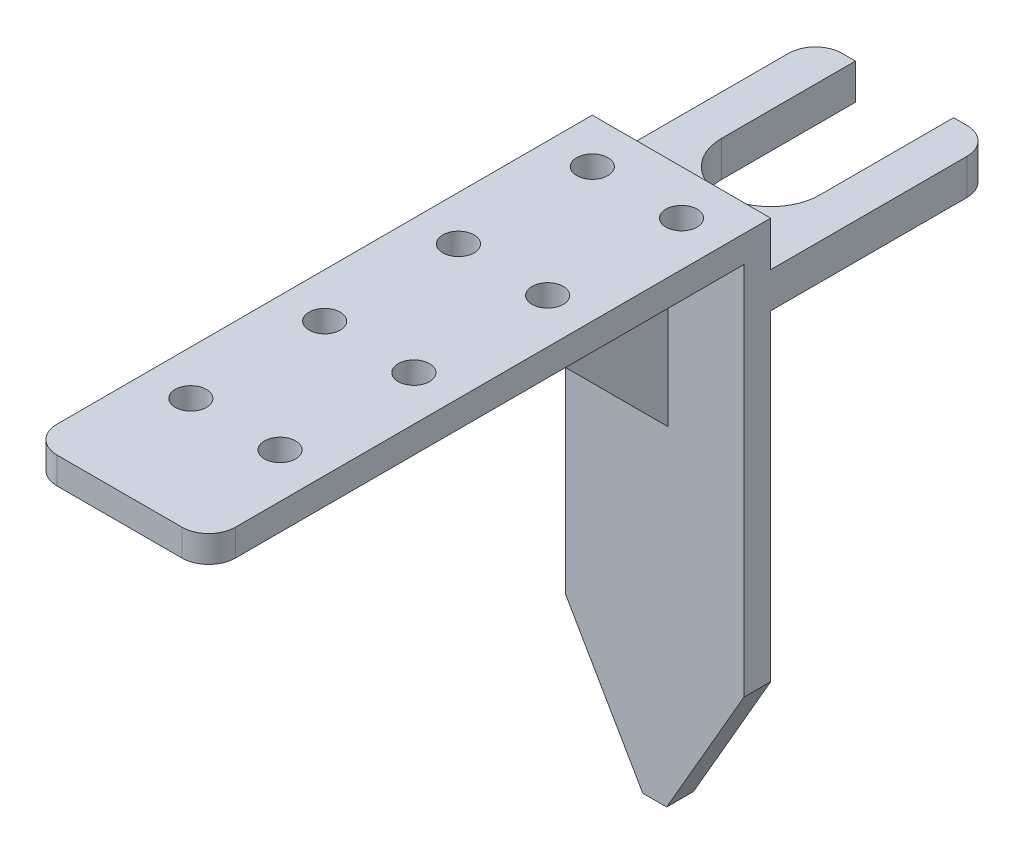
SolidWorks part; units mm, degrees
ref_plane "Front Plane" through (0, 0, 0) normal (0, 0, 1) x (1, 0, 0)
ref_plane "Top Plane" through (0, 0, 0) normal (0, 1, 0) x (1, 0, 0)
ref_plane "Right Plane" through (0, 0, 0) normal (1, 0, 0) x (0, 0, -1)
sketch "Sketch1" plane through (0, 0, 0) normal (0, 0, 1) x (1, 0, 0)
  line L1 (-10, 30) -> (10, 30)
  line L2 (-10, 30) -> (-10, -30)
  line L3 (-10, -30) -> (10, -30)
  line L4 (10, 30) -> (10, -30)
  line L5 (-10, 30) -> (10, -30) construction
  line L6 (-10, -30) -> (10, 30) construction
  point P0 (0, 0)
  dimension "D1" = 20
  dimension "D2" = 60
extrude "Boss-Extrude1" add sketch "Sketch1" along normal blind 3
sketch "Sketch2" plane through (0, 0, 3) normal (0, 0, 1) x (1, 0, 0)
  line L0 (10, -30) -> (10, 30) construction
  line L1 (-10, 30) -> (10, 30)
  line L2 (-10, 30) -> (-10, 27)
  line L3 (-10, 27) -> (10, 27)
  line L4 (10, 30) -> (10, 27)
  dimension "D1" = 3
extrude "Boss-Extrude2" add sketch "Sketch2" along normal blind 60
sketch "Sketch3" plane through (0, 27, 0) normal (0, -1, 0) x (1, 0, 0)
  line L0 (-10, 3) -> (10, 3) construction
  line L1 (-1.5, 3) -> (1.5, 3)
  line L2 (-1.5, 3) -> (-1.5, 18)
  line L3 (-1.5, 18) -> (1.5, 18)
  line L4 (1.5, 3) -> (1.5, 18)
  line L5 (0, 3) -> (0, 0) construction
  dimension "D1" = 3
  dimension "D2" = 15
extrude "Boss-Extrude3" add sketch "Sketch3" along normal blind 20
chamfer "Chamfer1" distance 15 angle 45 1 edges at (0, 7, 18)
sketch "Sketch4" plane through (0, 27, 0) normal (0, -1, 0) x (1, 0, 0)
  line L0 (-5, 5) -> (5, 5) construction
  line L1 (0, 5) -> (0, 0) construction
  circle A0 centre (-5, 5) radius 1.75
  circle A1 centre (5, 5) radius 1.75
  dimension "D1" = 3.5
  dimension "D2" = 3.5
  dimension "D3" = 10
  dimension "D4" = 5
extrude "Cut-Extrude1" cut sketch "Sketch4" against normal through all
pattern_linear "LPattern1" count 4 spacing 15 along (0, 0, 1) of "Cut-Extrude1"
chamfer "Chamfer2" distance 15 angle 30 2 edges at (-10, -30, 1.5) (10, -30, 1.5) first distance on face at (-10, 9, 22) first distance on face at (10, 9, 22)
fillet "Fillet1" radius 3 2 edges at (-10, 28.5, 63) (10, 28.5, 63)
sketch "Sketch5" plane through (0, 0, 0) normal (0, 0, -1) x (-1, 0, 0)
  line L0 (-10, -15) -> (-10, 30) construction
  line L1 (-10, 25) -> (10, 25)
  line L2 (-10, 25) -> (-10, 21)
  line L3 (-10, 21) -> (10, 21)
  line L4 (10, 25) -> (10, 21)
  line L5 (10, 30) -> (10, -15) construction
  line L6 (-10, 30) -> (10, 30) construction
  dimension "D1" = 5
  dimension "D2" = 4
extrude "Boss-Extrude4" add sketch "Sketch5" along normal blind 25
sketch "Sketch6" plane through (0, 25, 0) normal (0, 1, 0) x (1, 0, 0)
  line L0 (0, 0) -> (0, 10) construction
  line L1 (10, 0) -> (-10, 0) construction
  line L2 (-5.5, 10) -> (-5.5, 25)
  line L3 (-10, 25) -> (10, 25) construction
  line L4 (-5.5, 25) -> (5.5, 25)
  line L5 (5.5, 25) -> (5.5, 10)
  arc A0 (-5.5, 10) -> (5.5, 10) centre (0, 10) ccw
  dimension "D1" = 10
  dimension "D2" = 11
extrude "Cut-Extrude2" cut sketch "Sketch6" against normal through all
fillet "Fillet2" radius 3 2 edges at (-10, 23, -25) (10, 23, -25)
